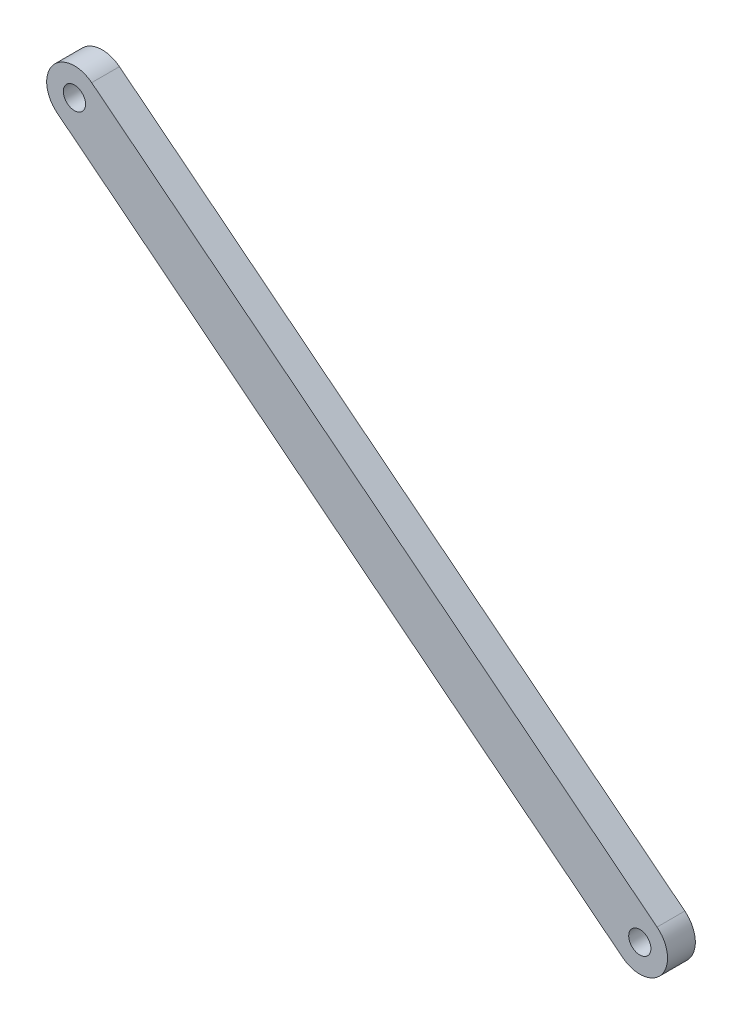
SolidWorks part; units mm, degrees
ref_plane "Front Plane" through (0, 0, 0) normal (0, 0, 1) x (1, 0, 0)
ref_plane "Top Plane" through (0, 0, 0) normal (0, 1, 0) x (1, 0, 0)
ref_plane "Right Plane" through (0, 0, 0) normal (1, 0, 0) x (0, 0, -1)
sketch "Sketch1" plane through (0, 0, 0) normal (0, 0, 1) x (1, 0, 0)
  line L0 (-127.9862, 136.916) -> (-26.1461, 56.1162)
  line L1 (-32.3614, 48.2824) -> (-134.2015, 129.0821)
  circle A0 centre (-29.2538, 52.1993) radius 2 construction
  circle A1 centre (-29.2538, 52.1993) radius 2
  circle A2 centre (-131.0938, 132.9991) radius 2 construction
  circle A3 centre (-131.0938, 132.9991) radius 2
  arc A4 (-26.1461, 56.1162) -> (-32.3614, 48.2824) centre (-29.2538, 52.1993) cw
  arc A5 (-134.2015, 129.0821) -> (-127.9862, 136.916) centre (-131.0938, 132.9991) cw
  dimension "D1" = 5
  dimension "D2" = 5
extrude "Boss-Extrude1" add sketch "Sketch1" along normal blind 5 from offset 5
